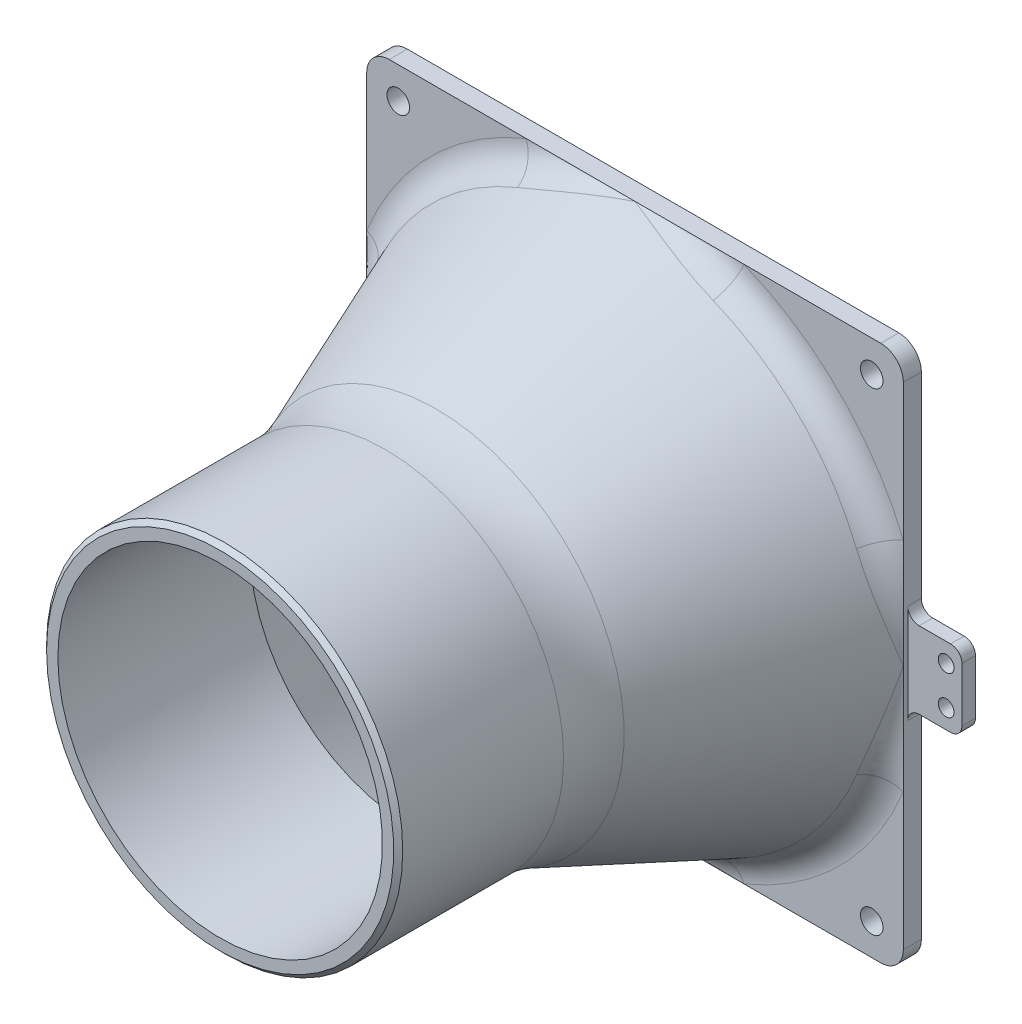
SolidWorks part; units mm, degrees
ref_plane "Plan de face" through (0, 0, 0) normal (0, 0, 1) x (1, 0, 0)
ref_plane "Plan de dessus" through (0, 0, 0) normal (0, 1, 0) x (1, 0, 0)
ref_plane "Plan de droite" through (0, 0, 0) normal (1, 0, 0) x (0, 0, -1)
sketch "Esquisse1" plane through (0, 0, 0) normal (0, 0, 1) x (1, 0, 0)
  line L1 (-59.5, -59.5) -> (59.5, -59.5)
  line L2 (-59.5, -59.5) -> (-59.5, 59.5)
  line L3 (-59.5, 59.5) -> (59.5, 59.5)
  line L4 (59.5, -59.5) -> (59.5, 59.5)
  line L5 (-59.5, -59.5) -> (59.5, 59.5) construction
  line L6 (-59.5, 59.5) -> (59.5, -59.5) construction
  circle A0 centre (0, 0) radius 56
  circle A1 centre (-52.5, 52.5) radius 2.5
  circle A2 centre (52.5, 52.5) radius 2.5
  circle A3 centre (52.5, -52.5) radius 2.5
  circle A4 centre (-52.5, -52.5) radius 2.5
  point P0 (0, 0)
  dimension "D3" = 3.5
  dimension "D4" = 5
  dimension "D1" = 119
  dimension "D2" = 119
  dimension "D5" = 7
  dimension "D6" = 7
  dimension "D7" = 2
  dimension "D8" = 2
extrude "Boss.-Extru.1" add sketch "Esquisse1" along normal blind 4
sketch "Esquisse2" plane through (0, 0, 0) normal (1, 0, 0) x (0, 0, -1)
  line L0 (-4, 59.5) -> (-53.5017, 39.5)
  line L3 (0, 0) -> (-140.1012, 0) construction
  line L4 (-53.5017, 39.5) -> (-96.0017, 39.5)
  line L5 (-4, 56) -> (-4, -56) construction
  line L6 (-4, 56) -> (-53.5017, 36)
  line L7 (-4, 59.5) -> (-4, -59.5) construction
  line L8 (-53.5017, 36) -> (-96.0017, 36)
  line L9 (-96.0017, 36) -> (-96.0017, 39.5)
  line L10 (-4, 59.5) -> (-4, 56)
  line L11 (-4, 59.5) -> (-4, 56)
  dimension "D1" = 39.5
  dimension "D2" = 68
  dimension "D3" = 3.5
  dimension "D4" = 42.5
revolve "Révolution1" add sketch "Esquisse2" angle 360 about L3 region at (0, 57.75, 4.9496)
fillet "Congé1" radius 7 4 edges at (-42.0729, 42.0729, 4) (-42.0729, -42.0729, 4) (42.0729, -42.0729, 4) (42.0729, 42.0729, 4)
fillet "Congé2" radius 30 1 edges at (-39.5, 0, 53.5017)
chamfer "Chanfrein1" distance 1 angle 45 1 edges at (-39.5, 0, 96.0017)
sketch "Esquisse3" plane through (59.5, 0, 0) normal (1, 0, 0) x (0, 0, -1)
  line L0 (0, -59.5) -> (0, 59.5) construction
  line L1 (0, 8.5) -> (-3, 8.5)
  line L2 (0, 8.5) -> (0, -8.5)
  line L3 (0, -8.5) -> (-3, -8.5)
  line L4 (-3, 8.5) -> (-3, -8.5)
  line L5 (0, 0) -> (5.8093, 0) construction
  dimension "D1" = 3
  dimension "D2" = 17
extrude "Boss.-Extru.2" add sketch "Esquisse3" along normal blind 12
sketch "Esquisse4" plane through (0, 0, 0) normal (0, 0, -1) x (-1, 0, 0)
  line L0 (-68, 7.9556) -> (-68, -8.035) construction
  line L1 (-71.5, -8.5) -> (-71.5, 8.5) construction
  line L3 (-71.5, -8.5) -> (-59.5, -8.5) construction
  line L4 (-71.5, 8.5) -> (-59.5, 8.5) construction
  circle A2 centre (-68, 4.25) radius 1.75
  circle A3 centre (-68, -4.25) radius 1.75
  dimension "D1" = 3.5
  dimension "D2" = 3.5
  dimension "D3" = 2.5
  dimension "D4" = 2.5
extrude "Enlèv. mat.-Extru.1" cut sketch "Esquisse4" against normal through all
fillet "Congé3" radius 5 4 edges at (59.5, -59.5, 2) (-59.5, -59.5, 2) (-59.5, 59.5, 2) (59.5, 59.5, 2)
fillet "Congé4" radius 2.5 4 edges at (59.5, -8.5, 1.5) (71.5, -8.5, 1.5) (71.5, 8.5, 1.5) (59.5, 8.5, 1.5)
